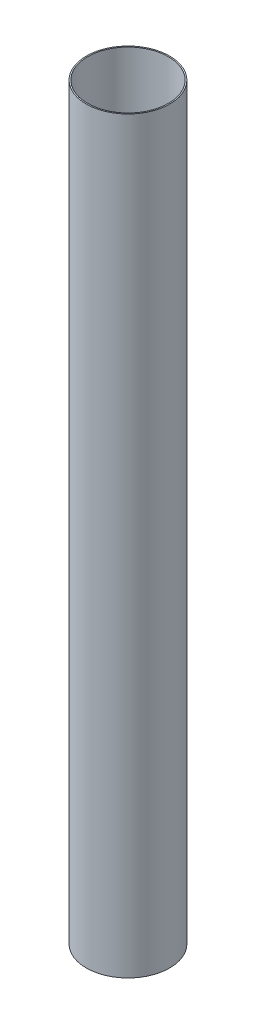
SolidWorks part; units mm, degrees
material "A-Glass Fiber"
ref_plane "Front Plane" through (0, 0, 0) normal (0, 0, 1) x (1, 0, 0)
ref_plane "Top Plane" through (0, 0, 0) normal (0, 1, 0) x (1, 0, 0)
ref_plane "Right Plane" through (0, 0, 0) normal (1, 0, 0) x (0, 0, -1)
sketch "Sketch1" plane through (0, 0, 0) normal (0, 1, 0) x (1, 0, 0)
  circle A0 centre (0, 0) radius 78.35
  circle A1 centre (0, 0) radius 80.75
  dimension "D1" = 156.7
  dimension "D2" = 2.4
extrude "Boss-Extrude1" add sketch "Sketch1" along normal blind 725 and the other way blind 725
